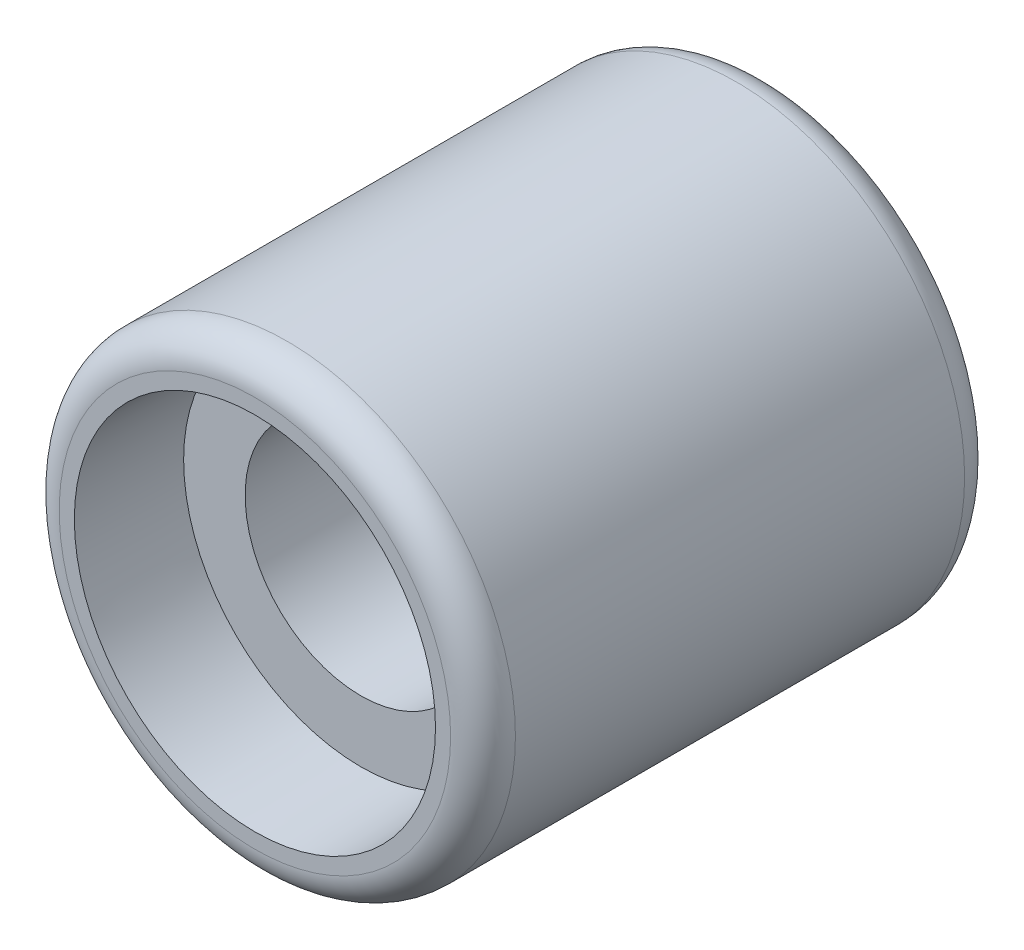
SolidWorks part; units mm, degrees
extrude "Body" add sketch "BodySch" along normal mid plane 85.852
sketch "BodySch" plane through (0, 0, 0) normal (0, 0, 1) x (1, 0, 0)
  circle A0 centre (0, 0) radius 38.1
  dimension "Dia" = 76.2
material "PW90:Mi:0:191:Ar:0:-1:C1:1:2:3:Re:17:Ts:18:19:20:21:22:23:"
ref_plane "Front" through (0, 0, 0) normal (0, 0, 1) x (1, 0, 0)
ref_plane "Top" through (0, 0, 0) normal (0, 1, 0) x (1, 0, 0)
ref_plane "Right" through (0, 0, 0) normal (1, 0, 0) x (0, 0, -1)
sketch "FlowSch" plane through (0, 0, -42.926) normal (0, 0, 1) x (1, 0, 0)
  circle A0 centre (0, 0) radius 19.337
  dimension "Dia" = 38.674
extrude "Flow" cut sketch "FlowSch" along normal up to surface (85.852 mm away) up to face at (38.1, 0, 42.926)
sketch "ThreadSch" plane through (0, 0, 0) normal (1, 0, 0) x (0, 0, -1)
  line L0 (0, 0) -> (-42.926, 0) construction
  line L1 (-42.926, 0) -> (42.926, 0) construction
  line L2 (-25.2222, 0) -> (-25.2222, 29.6113)
  line L3 (-25.2222, 29.6113) -> (-42.926, 30.1625)
  line L4 (-42.926, 30.1625) -> (-42.926, 0)
  line L5 (-42.926, 0) -> (-25.2222, 0)
  line L6 (-42.926, 38.1) -> (-42.926, -38.1) construction
  dimension "D1" = 1.783
revolve "Thread" cut sketch "ThreadSch" angle 360 about L0
fillet "Fillet1" radius 5.4127 2 edges at (38.1, 0, 42.926) (38.1, 0, -42.926)
mirror "Mirror1" about plane through (0, 0, 0) normal (0, 0, 1) of "Thread"
sketch "Sketch1" plane through (0, 0, 0) normal (1, 0, 0) x (0, 0, -1)
  line L0 (-37.5133, 0) -> (37.5133, 0) construction
  line L1 (25.2222, -29.6113) -> (25.2222, 29.6113) construction
  line L2 (-25.2222, 29.6113) -> (-25.2222, -29.6113) construction
  point P0 (0, 0)
  point P1 (-25.2222, 0)
  point P3 (25.2222, 0)
other "CPoint1" parameters "Diameter"=50.8, "StubLength"=0
ref_axis "Axis1" through (0, 0, -35.2222) along (0, 0, 1)
other "CPoint2" parameters "Diameter"=50.8, "StubLength"=0
ref_axis "Axis2" through (0, 0, 35.2222) along (0, 0, -1)
other "RPoint1"
equation "\"EdgeRadius@Fillet1\" =  ( \"Dia@ThreadSch\" - \"Dia@FlowSch\" )  / 4"
